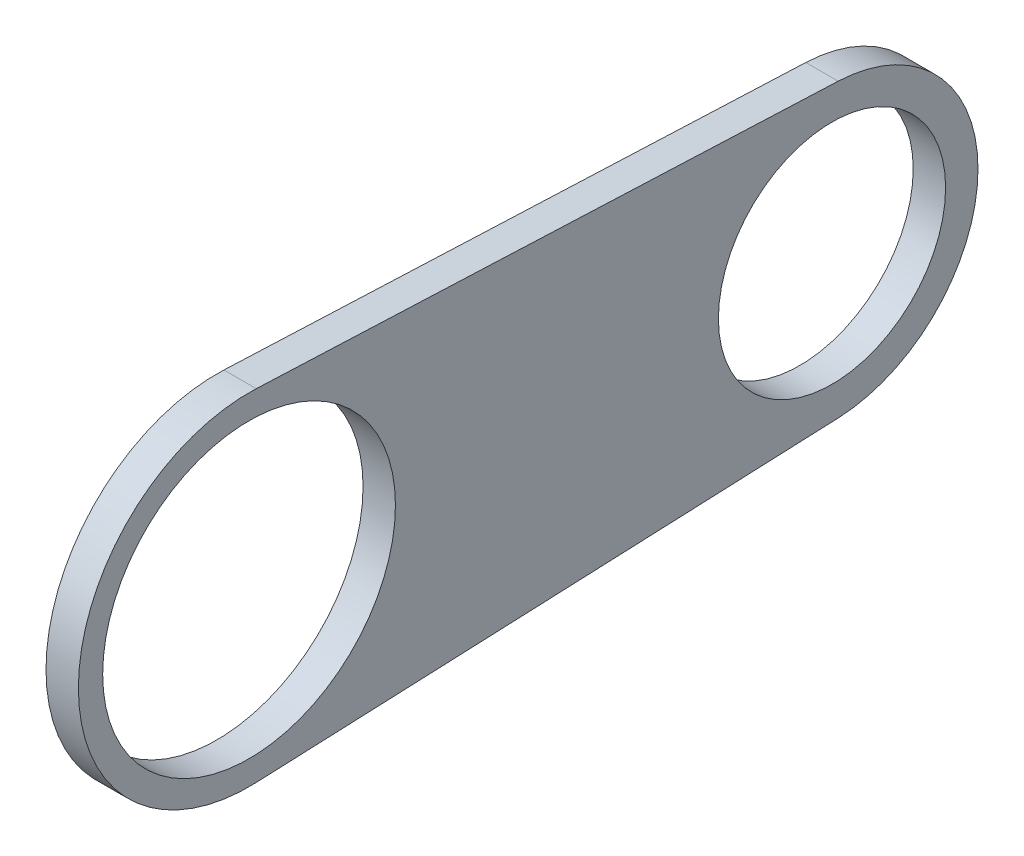
SolidWorks part; units mm, degrees
material "6061-T6 (SS)"
ref_plane "Front" through (0, 0, 0) normal (0, 0, 1) x (1, 0, 0)
ref_plane "Top" through (0, 0, 0) normal (0, 1, 0) x (1, 0, 0)
ref_plane "Right" through (0, 0, 0) normal (1, 0, 0) x (0, 0, -1)
sketch "Sketch1" plane through (0, 0, 0) normal (1, 0, 0) x (0, 0, -1)
  line L0 (-27.8667, 16.7173) -> (29.1809, 14.3001)
  line L3 (-27.8667, -16.7173) -> (29.1809, -14.3001)
  line L4 (-28.575, 0) -> (28.575, 0) construction
  circle A2 centre (-28.575, 0) radius 14.351
  circle A3 centre (28.575, 0) radius 11.1379
  arc A4 (29.1809, -14.3001) -> (29.1809, 14.3001) centre (28.575, 0) ccw
  arc A5 (-27.8667, 16.7173) -> (-27.8667, -16.7173) centre (-28.575, 0) ccw
  point P13 (0, 0)
  dimension "D1" = 28.702
  dimension "D2" = 2.3812
  dimension "D4" = 22.2758
  dimension "D3" = 3.175
  dimension "D5" = 57.15
extrude "Boss-Extrude1" add sketch "Sketch1" along normal blind 3.175
